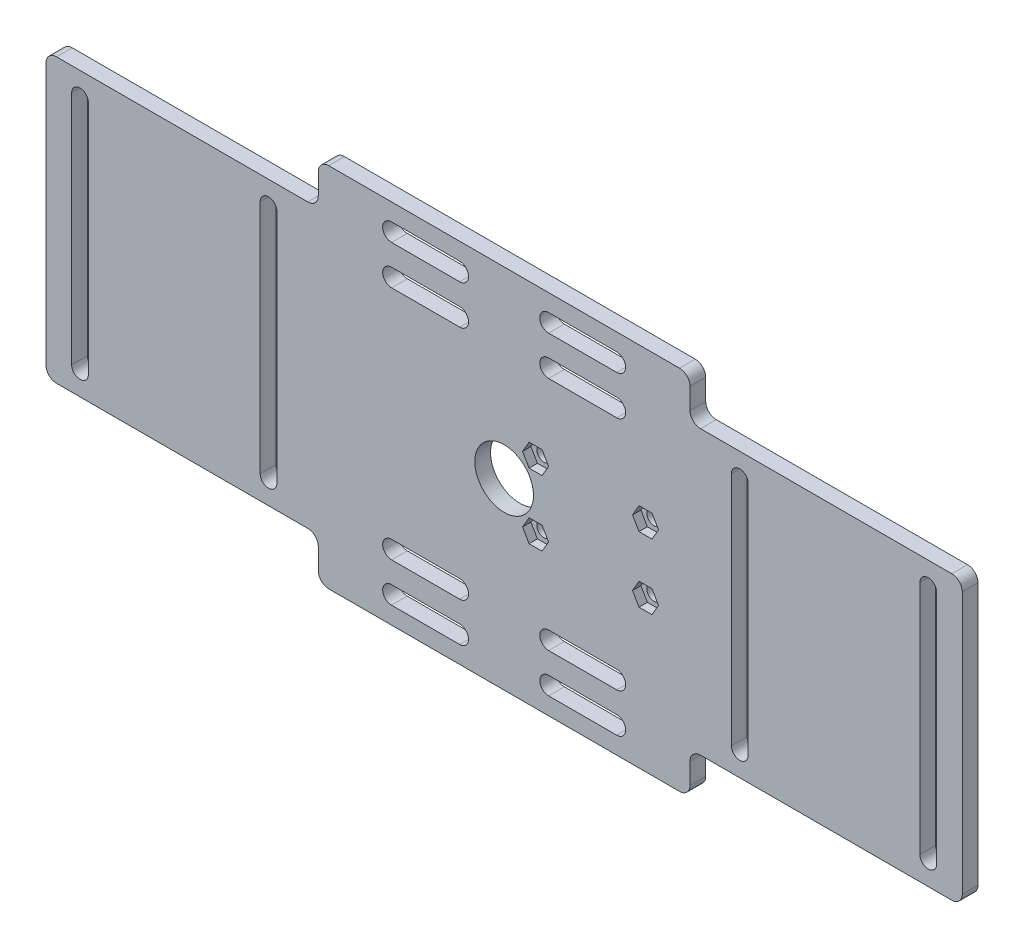
SolidWorks part; units mm, degrees
ref_plane "前基準面" through (0, 0, 0) normal (0, 0, 1) x (1, 0, 0)
ref_plane "上基準面" through (0, 0, 0) normal (0, 1, 0) x (1, 0, 0)
ref_plane "右基準面" through (0, 0, 0) normal (1, 0, 0) x (0, 0, -1)
sketch "草圖1" plane through (0, 0, 0) normal (0, 0, 1) x (1, 0, 0)
  line L0 (35.5, 33) -> (35.5, 29)
  line L1 (-33.5, 35) -> (33.5, 35)
  line L2 (-87.5, 25) -> (-87.5, -25)
  line L3 (-33.5, -35) -> (33.5, -35)
  line L4 (87.5, 25) -> (87.5, -25)
  line L5 (-87.5, 35) -> (87.5, -35) construction
  line L6 (-87.5, -35) -> (87.5, 35) construction
  line L7 (37.5, 27) -> (85.5, 27)
  line L8 (0, 71.4811) -> (0, -70.0061) construction
  line L9 (-113.0104, 0) -> (128.372, 0) construction
  line L10 (-37.5, 27) -> (-85.5, 27)
  line L11 (-35.5, 33) -> (-35.5, 29)
  line L12 (37.5, -27) -> (85.5, -27)
  line L13 (35.5, -33) -> (35.5, -29)
  line L14 (-35.5, -33) -> (-35.5, -29)
  line L15 (-37.5, -27) -> (-85.5, -27)
  arc A0 (35.5, 33) -> (33.5, 35) centre (33.5, 33) ccw
  arc A1 (37.5, 27) -> (35.5, 29) centre (37.5, 29) cw
  arc A2 (87.5, 25) -> (85.5, 27) centre (85.5, 25) ccw
  arc A3 (-87.5, 25) -> (-85.5, 27) centre (-85.5, 25) cw
  arc A4 (-37.5, 27) -> (-35.5, 29) centre (-37.5, 29) ccw
  arc A5 (-35.5, 33) -> (-33.5, 35) centre (-33.5, 33) cw
  arc A6 (87.5, -25) -> (85.5, -27) centre (85.5, -25) cw
  arc A7 (37.5, -27) -> (35.5, -29) centre (37.5, -29) ccw
  arc A8 (35.5, -33) -> (33.5, -35) centre (33.5, -33) cw
  arc A9 (-35.5, -33) -> (-33.5, -35) centre (-33.5, -33) ccw
  arc A10 (-37.5, -27) -> (-35.5, -29) centre (-37.5, -29) cw
  arc A11 (-87.5, -25) -> (-85.5, -27) centre (-85.5, -25) ccw
  point P0 (0, 0)
  point P13 (35.5, 27)
  point P29 (-35.5, 27)
  point P39 (35.5, -27)
  point P49 (-35.5, -27)
  dimension "D1" = 2
  dimension "D2" = 2
  dimension "D3" = 2
  dimension "D4" = 175
  dimension "D5" = 70
  dimension "D6" = 8
  dimension "D7" = 52
extrude "填料-伸長1" add sketch "草圖1" along normal blind 3
sketch "草圖2" plane through (0, 0, 3) normal (0, 0, 1) x (1, 0, 0)
  line L0 (-1000, 0) -> (49000, 0) construction
  line L1 (45, -986.1952) -> (45, 49013.8048) construction
  line L2 (-81, -962.7943) -> (-81, 49037.2057) construction
  line L3 (45, -22.5) -> (45, 22.5) construction
  line L4 (43.4, -22.5) -> (43.4, 22.5)
  line L5 (46.6, -22.5) -> (46.6, 22.5)
  line L6 (-45, -1000) -> (-45, 49000) construction
  line L7 (-45, -22.5) -> (-45, 22.5) construction
  line L8 (-46.6, -22.5) -> (-46.6, 22.5)
  line L9 (-43.4, -22.5) -> (-43.4, 22.5)
  line L10 (0, -1000) -> (0, 49000) construction
  line L11 (-1010.5287, 30) -> (48989.4713, 30) construction
  line L12 (-1007.193, -30) -> (48992.807, -30) construction
  line L13 (21.5, -30) -> (8.5, -30) construction
  line L16 (6, -996.0597) -> (6, 49003.9403) construction
  line L19 (81, -968.4295) -> (81, 49031.5705) construction
  line L20 (-81, -22.5) -> (-81, 22.5) construction
  line L21 (-82.6, -22.5) -> (-82.6, 22.5)
  line L22 (-79.4, -22.5) -> (-79.4, 22.5)
  line L23 (81, -22.5) -> (81, 22.5) construction
  line L24 (79.4, -22.5) -> (79.4, 22.5)
  line L25 (82.6, -22.5) -> (82.6, 22.5)
  line L26 (27, -997.4467) -> (27, 49002.5533) construction
  line L27 (-1014.4971, -6.25) -> (48985.5029, -6.25) construction
  line L28 (-1015.8254, 6.25) -> (48984.1746, 6.25) construction
  line L29 (-33.5, -35) -> (33.5, -35) construction
  line L30 (21.5, -31.7) -> (8.5, -31.7)
  line L33 (21.5, -28.3) -> (8.5, -28.3)
  line L34 (-21.5, -30) -> (-8.5, -30) construction
  line L35 (-21.5, -31.7) -> (-8.5, -31.7)
  line L36 (-21.5, -28.3) -> (-8.5, -28.3)
  line L37 (21.5, 30) -> (8.5, 30) construction
  line L38 (21.5, 31.7) -> (8.5, 31.7)
  line L39 (21.5, 28.3) -> (8.5, 28.3)
  line L40 (-21.5, 30) -> (-8.5, 30) construction
  line L41 (-21.5, 31.7) -> (-8.5, 31.7)
  line L42 (-21.5, 28.3) -> (-8.5, 28.3)
  line L43 (21.5, 22.5) -> (8.5, 22.5) construction
  line L44 (21.5, 24.2) -> (8.5, 24.2)
  line L45 (21.5, 20.8) -> (8.5, 20.8)
  line L46 (-21.5, 22.5) -> (-8.5, 22.5) construction
  line L47 (-21.5, 24.2) -> (-8.5, 24.2)
  line L48 (-21.5, 20.8) -> (-8.5, 20.8)
  line L49 (-21.5, -22.5) -> (-8.5, -22.5) construction
  line L50 (-21.5, -24.2) -> (-8.5, -24.2)
  line L51 (-21.5, -20.8) -> (-8.5, -20.8)
  line L52 (21.5, -22.5) -> (8.5, -22.5) construction
  line L53 (21.5, -24.2) -> (8.5, -24.2)
  line L54 (21.5, -20.8) -> (8.5, -20.8)
  arc A0 (43.4, -22.5) -> (46.6, -22.5) centre (45, -22.5) ccw
  arc A1 (46.6, 22.5) -> (43.4, 22.5) centre (45, 22.5) ccw
  arc A2 (-46.6, -22.5) -> (-43.4, -22.5) centre (-45, -22.5) ccw
  arc A3 (-43.4, 22.5) -> (-46.6, 22.5) centre (-45, 22.5) ccw
  arc A12 (-82.6, -22.5) -> (-79.4, -22.5) centre (-81, -22.5) ccw
  arc A13 (-79.4, 22.5) -> (-82.6, 22.5) centre (-81, 22.5) ccw
  arc A14 (79.4, -22.5) -> (82.6, -22.5) centre (81, -22.5) ccw
  arc A15 (82.6, 22.5) -> (79.4, 22.5) centre (81, 22.5) ccw
  circle A16 centre (0, 0) radius 5.6
  circle A17 centre (27, 6.25) radius 1.35
  circle A18 centre (6, 6.25) radius 1.35
  circle A19 centre (6, -6.25) radius 1.35
  circle A20 centre (27, -6.25) radius 1.35
  arc A23 (21.5, -31.7) -> (21.5, -28.3) centre (21.5, -30) ccw
  arc A24 (8.5, -28.3) -> (8.5, -31.7) centre (8.5, -30) ccw
  arc A25 (-21.5, -31.7) -> (-21.5, -28.3) centre (-21.5, -30) cw
  arc A26 (-8.5, -28.3) -> (-8.5, -31.7) centre (-8.5, -30) cw
  arc A27 (21.5, 31.7) -> (21.5, 28.3) centre (21.5, 30) cw
  arc A28 (8.5, 28.3) -> (8.5, 31.7) centre (8.5, 30) cw
  arc A29 (-21.5, 31.7) -> (-21.5, 28.3) centre (-21.5, 30) ccw
  arc A30 (-8.5, 28.3) -> (-8.5, 31.7) centre (-8.5, 30) ccw
  arc A31 (21.5, 24.2) -> (21.5, 20.8) centre (21.5, 22.5) cw
  arc A32 (8.5, 20.8) -> (8.5, 24.2) centre (8.5, 22.5) cw
  arc A33 (-21.5, 24.2) -> (-21.5, 20.8) centre (-21.5, 22.5) ccw
  arc A34 (-8.5, 20.8) -> (-8.5, 24.2) centre (-8.5, 22.5) ccw
  arc A35 (-21.5, -24.2) -> (-21.5, -20.8) centre (-21.5, -22.5) cw
  arc A36 (-8.5, -20.8) -> (-8.5, -24.2) centre (-8.5, -22.5) cw
  arc A37 (21.5, -24.2) -> (21.5, -20.8) centre (21.5, -22.5) ccw
  arc A38 (8.5, -20.8) -> (8.5, -24.2) centre (8.5, -22.5) ccw
  point P9 (45, 0)
  point P16 (-45, 0)
  point P31 (15, -30)
  point P47 (-81, 0)
  point P54 (81, 0)
  point P72 (-15, -30)
  point P81 (15, 30)
  point P88 (-15, 30)
  point P97 (15, 22.5)
  point P102 (-15, 22.5)
  point P110 (-15, -22.5)
  point P116 (15, -22.5)
  dimension "D10" = 1.7
  dimension "D20" = 11.2
  dimension "D21" = 2.7
  dimension "D27" = 7.5
  dimension "D2" = 45
  dimension "D3" = 3.2
  dimension "D4" = 90
  dimension "D5" = 45
  dimension "D6" = 3.2
  dimension "D7" = 45
  dimension "D8" = 60
  dimension "D9" = 30
  dimension "D11" = 13
  dimension "D12" = 12.5
  dimension "D13" = 21
  dimension "D14" = 162
  dimension "D15" = 81
  dimension "D16" = 3.2
  dimension "D17" = 45
  dimension "D18" = 45
  dimension "D19" = 3.2
  dimension "D22" = 28.75
  dimension "D23" = 6
  dimension "D24" = 8.5
  dimension "D25" = 2
  dimension "D28" = 7.5
  dimension "D26" = 2
extrude "除料-伸長1" cut sketch "草圖2" against normal through all
sketch "草圖3" plane through (0, 0, 3) normal (0, 0, 1) x (1, 0, 0)
  line L0 (29.4826, -6.25) -> (28.2413, -4.1)
  line L1 (8.4826, -6.25) -> (7.2413, -4.1)
  line L2 (7.2413, -4.1) -> (4.7587, -4.1)
  line L3 (4.7587, -4.1) -> (3.5174, -6.25)
  line L4 (3.5174, -6.25) -> (4.7587, -8.4)
  line L5 (4.7587, -8.4) -> (7.2413, -8.4)
  line L6 (7.2413, -8.4) -> (8.4826, -6.25)
  line L7 (28.2413, -4.1) -> (25.7587, -4.1)
  line L8 (25.7587, -4.1) -> (24.5174, -6.25)
  line L9 (24.5174, -6.25) -> (25.7587, -8.4)
  line L10 (25.7587, -8.4) -> (28.2413, -8.4)
  line L11 (28.2413, -8.4) -> (29.4826, -6.25)
  line L12 (29.4826, 6.25) -> (28.2413, 8.4)
  line L13 (28.2413, 8.4) -> (25.7587, 8.4)
  line L14 (25.7587, 8.4) -> (24.5174, 6.25)
  line L15 (24.5174, 6.25) -> (25.7587, 4.1)
  line L16 (25.7587, 4.1) -> (28.2413, 4.1)
  line L17 (28.2413, 4.1) -> (29.4826, 6.25)
  line L18 (8.4826, 6.25) -> (7.2413, 8.4)
  line L19 (7.2413, 8.4) -> (4.7587, 8.4)
  line L20 (4.7587, 8.4) -> (3.5174, 6.25)
  line L21 (3.5174, 6.25) -> (4.7587, 4.1)
  line L22 (4.7587, 4.1) -> (7.2413, 4.1)
  line L23 (7.2413, 4.1) -> (8.4826, 6.25)
  circle A0 centre (6, -6.25) radius 2.15 construction
  circle A3 centre (27, -6.25) radius 2.15 construction
  circle A4 centre (27, 6.25) radius 2.15 construction
  circle A5 centre (6, 6.25) radius 2.15 construction
  dimension "D1" = 4.3
  dimension "D2" = 2
  dimension "D3" = 2
extrude "除料-伸長2" cut sketch "草圖3" against normal blind 1.6
sketch "草圖4" plane through (0, 0, 0) normal (0, 0, -1) x (-1, 0, 0)
  circle A0 centre (-27, 6.25) radius 1.35
  circle A1 centre (-27, -6.25) radius 1.25
  circle A2 centre (-6, 6.25) radius 1.25
  circle A3 centre (-6, -6.25) radius 1.25
  circle A4 centre (-27, 6.25) radius 2.1
  circle A5 centre (-27, -6.25) radius 2
  circle A6 centre (-6, 6.25) radius 2
  circle A7 centre (-6, -6.25) radius 2
  circle A8 centre (-27, 6.25) radius 1.35 construction
  dimension "D1" = 0.75
extrude "填料-伸長2" add sketch "草圖4" along normal blind 2
chamfer "導角1" distance 0.5 angle 30 4 edges at (25.65, 6.25, -2) (4.75, 6.25, -2) (4.75, -6.25, -2) (25.75, -6.25, -2) first distance on face at (24.9, 6.25, -2) first distance on face at (4, 6.25, -2) first distance on face at (4, -6.25, -2) first distance on face at (25, -6.25, -2)
fillet "圓角2" radius 0.5 4 edges at (29.1, 6.25, 0) (8, 6.25, 0) (8, -6.25, 0) (29, -6.25, 0)
